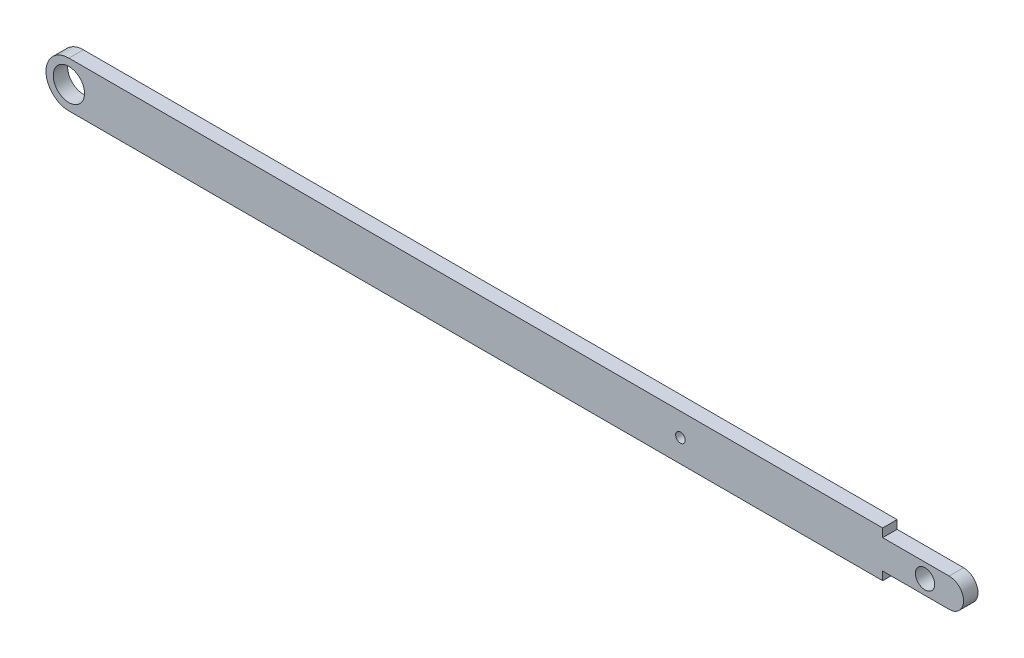
SolidWorks part; units mm, degrees
material "Gray Cast Iron"
ref_plane "Front Plane" through (0, 0, 0) normal (0, 0, 1) x (1, 0, 0)
ref_plane "Top Plane" through (0, 0, 0) normal (0, 1, 0) x (1, 0, 0)
ref_plane "Right Plane" through (0, 0, 0) normal (1, 0, 0) x (0, 0, -1)
sketch "Sketch1" plane through (0, 0, 0) normal (0, 0, 1) x (1, 0, 0)
  line L0 (0, -4.75) -> (169, -4.75)
  line L1 (169, -4.75) -> (169, -3)
  line L2 (169, -3) -> (182.8, -3)
  line L3 (182.8, 3) -> (169, 3)
  line L4 (169, 3) -> (169, 4.75)
  line L5 (169, 4.75) -> (0, 4.75)
  arc A0 (0, 4.75) -> (0, -4.75) centre (0, 0) ccw
  arc A1 (182.8, -3) -> (182.8, 3) centre (182.8, 0) ccw
extrude "Boss-Extrude1" add sketch "Sketch1" along normal mid plane 3
sketch "Sketch2" plane through (0, 0, 0) normal (0, 0, 1) x (1, 0, 0)
  circle A0 centre (0, 0) radius 3.25
  circle A1 centre (127, 0) radius 1
  circle A2 centre (177.8, 0) radius 2
  dimension "D1" = 6.5
  dimension "D2" = 2
  dimension "D3" = 4
extrude "Cut-Extrude1" cut sketch "Sketch2" against normal mid plane 40
